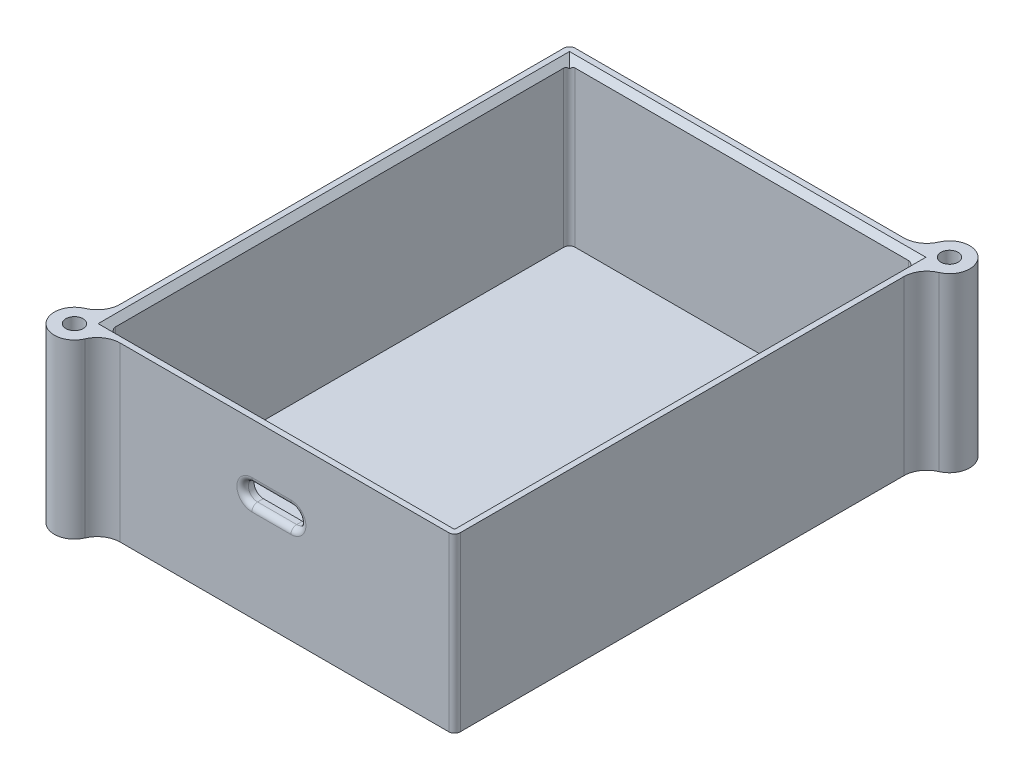
SolidWorks part; units mm, degrees
ref_plane "Front Plane" through (0, 0, 0) normal (0, 0, 1) x (1, 0, 0)
ref_plane "Top Plane" through (0, 0, 0) normal (0, 1, 0) x (1, 0, 0)
ref_plane "Right Plane" through (0, 0, 0) normal (1, 0, 0) x (0, 0, -1)
sketch "Sketch1" plane through (0, 0, 0) normal (0, 1, 0) x (1, 0, 0)
  line L0 (0, 0) -> (60, 0)
  line L1 (60, 0) -> (60, -80)
  line L2 (60, -80) -> (0, -80)
  line L3 (0, -80) -> (0, 0)
  line L4 (-2, -82) -> (-2, 2)
  line L5 (-2, 2) -> (62, 2)
  line L6 (62, 2) -> (62, -82)
  line L7 (62, -82) -> (-2, -82)
  dimension "D1" = 60
  dimension "D2" = 80
  dimension "D3" = 2
extrude "Boss-Extrude1" add sketch "Sketch1" along normal blind 30
ref_plane "HOLE_MIRROR_PLANE" through (-0.3013, 0, 0.2296) normal (0.7954, 0, -0.606) x (-0.606, 0, -0.7954)
sketch "Sketch2" plane through (0, 0, 0) normal (0, 1, 0) x (1, 0, 0)
  line L0 (-2, -82) -> (-6.2426, -86.2426) construction
  line L1 (-6.2426, -86.2426) -> (-3.0607, -83.0607) construction
  line L7 (62, 2) -> (66.2426, 6.2426) construction
  line L8 (66.2426, 6.2426) -> (63.0607, 3.0607) construction
  circle A0 centre (-3.0607, -83.0607) radius 1.5
  circle A1 centre (-3.0607, -83.0607) radius 3.5
  circle A2 centre (63.0607, 3.0607) radius 1.5
  circle A3 centre (63.0607, 3.0607) radius 3.5
  dimension "D3" = 3
  dimension "D4" = 7
  dimension "D7" = 3
  dimension "D8" = 7
  dimension "D1" = 6
  dimension "D2" = 4.5
  dimension "D5" = 6
  dimension "D6" = 4.5
extrude "Boss-Extrude2" add sketch "Sketch2" along normal blind 30
ref_plane "USBC_HOLE_PLANE" through (0, 0, 82) normal (0, 0, 1) x (1, 0, 0)
sketch "Sketch4" plane through (0, 0, 82) normal (0, 0, 1) x (1, 0, 0)
  line L0 (30.1413, 0) -> (30.1413, 17) construction
  line L1 (0.2748, 0) -> (62, 0) construction
  line L2 (30.1413, 17) -> (30.1413, 18.6) construction
  line L3 (30.1413, 18.6) -> (25.1413, 18.6) construction
  line L4 (30.1413, 18.6) -> (30.1413, 20.2) construction
  line L5 (25.1413, 18.6) -> (26.7413, 18.6) construction
  line L6 (30.1413, 20.2) -> (26.7413, 20.2)
  line L7 (30.1413, 17) -> (26.7413, 17)
  line L8 (30.1413, 18.6) -> (35.1413, 18.6) construction
  line L9 (35.1413, 18.6) -> (33.5413, 18.6) construction
  line L10 (30.1413, 20.2) -> (33.5413, 20.2)
  line L11 (30.1413, 17) -> (33.5413, 17)
  arc A0 (26.7413, 17) -> (26.7413, 20.2) centre (26.7413, 18.6) cw
  arc A1 (33.5413, 20.2) -> (33.5413, 17) centre (33.5413, 18.6) cw
  dimension "D1" = 17
  dimension "D2" = 1.6
  dimension "D3" = 5
  dimension "D4" = 1.6
  dimension "D5" = 1.6
  dimension "D6" = 5
  dimension "D7" = 1.6
extrude "Cut-Extrude1" cut sketch "Sketch4" against normal blind 30
fillet "Fillet2" radius 1 4 edges at (25.1413, 18.6, 82) (30.1413, 20.2, 82) (35.1413, 18.6, 82) (30.1413, 17, 82)
fillet "Fillet3" radius 4 4 edges at (62, 15, 0.2748) (59.7252, 15, -2) (-2, 15, 79.7252) (0.2748, 15, 82)
chamfer "Chamfer1" distance 1 angle 45 4 edges at (30, 30, 0) (60, 30, 40) (0, 30, 40) (30, 30, 80)
fillet "Fillet4" radius 1 2 edges at (-2, 15, -2) (62, 15, 82)
fillet "Fillet5" radius 1 4 edges at (60, 14.5, 80) (60, 14.5, 0) (0, 14.5, 0) (0, 14.5, 80)
sketch "Sketch6" plane through (0, 0, 0) normal (1, 0, 0) x (0, 0, -1)
  line L0 (-81, 0) -> (-81, 2)
  line L1 (-81, 30) -> (-81, 0) construction
  line L10 (-81, 2) -> (1.0534, 2)
  line L11 (1.0534, 2) -> (1.0534, 0)
  line L12 (-0.1593, 0) -> (6.5607, 0) construction
  line L13 (1.0534, 0) -> (-81, 0)
  dimension "D1" = 2
extrude "Boss-Extrude3" add sketch "Sketch6" along normal up to next contours L0 L10 L11 L13
